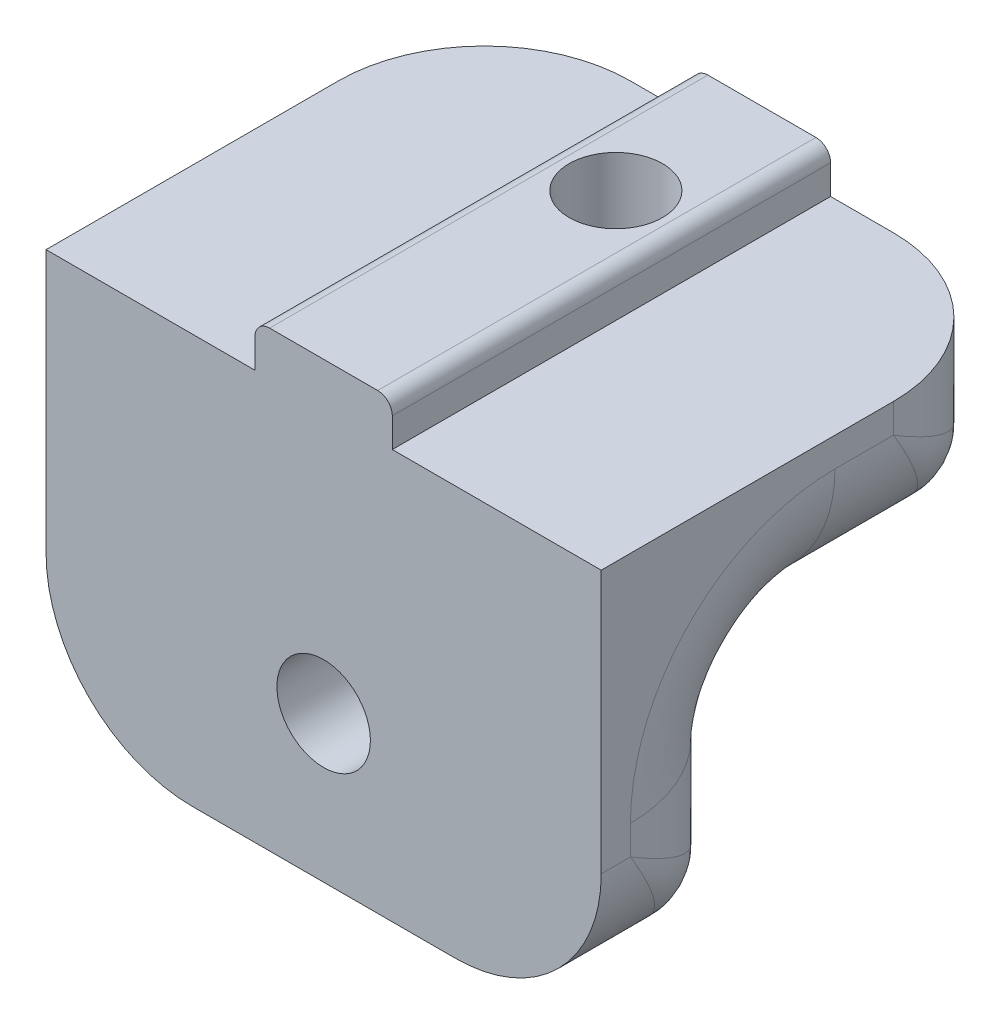
SolidWorks part; units mm, degrees
material "ABS"
ref_plane "Front" through (0, 0, 0) normal (0, 0, 1) x (1, 0, 0)
ref_plane "Top" through (0, 0, 0) normal (0, 1, 0) x (1, 0, 0)
ref_plane "Right" through (0, 0, 0) normal (1, 0, 0) x (0, 0, -1)
sketch "Esquisse1" plane through (0, 0, 0) normal (1, 0, 0) x (0, 0, -1)
  line L0 (15, 0) -> (0, 0)
  line L1 (0, 0) -> (0, -14)
  dimension "D1" = 90
  dimension "D2" = 15
  dimension "D3" = 14
extrude "Extru.-Mince1" add sketch "Esquisse1" along normal mid plane 19 thin thin type one direction reverse wall 6
fillet "Congé2" radius 2 3 edges at (0, -14, -6) (0, -6, -15) (0, -6, -6)
sketch "Esquisse2" plane through (0, 0, 0) normal (0, 1, 0) x (1, 0, 0)
  line L3 (9.5, 0) -> (-9.5, 0) construction
  line L4 (9.5, 15) -> (-9.5, 15) construction
  circle A1 centre (0, 10) radius 1.6
  dimension "D1" = 10
  dimension "D2" = 5
  dimension "D3" = 3.2
extrude "Enlèv. mat.-Extru.1" cut sketch "Esquisse2" against normal through all
sketch "Esquisse3" plane through (0, 0, 0) normal (0, 0, 1) x (1, 0, 0)
  line L0 (9.5, -14) -> (-9.5, -14) construction
  line L2 (9.5, 0) -> (-9.5, 0) construction
  circle A0 centre (0, -9) radius 1.6
  dimension "D1" = 5
  dimension "D2" = 3.2
  dimension "D3" = 9
extrude "Enlèv. mat.-Extru.2" cut sketch "Esquisse3" against normal through all
sketch "Esquisse4" plane through (0, 0, 0) normal (0, 1, 0) x (1, 0, 0)
  circle A0 centre (0, 10) radius 3
  circle A1 centre (0, 10) radius 1.6 construction
  dimension "D1" = 6
extrude "Enlèv. mat.-Extru.3" cut sketch "Esquisse4" against normal through all from offset 2.5 offset against normal yes
sketch "Esquisse5" plane through (0, 0, 0) normal (0, 0, 1) x (1, 0, 0)
  line L13 (-1.5877, -6.25) -> (-3.1754, -9)
  line L14 (-3.1754, -9) -> (-1.5877, -11.75)
  line L15 (-1.5877, -11.75) -> (1.5877, -11.75)
  line L16 (1.5877, -11.75) -> (3.1754, -9)
  line L17 (3.1754, -9) -> (1.5877, -6.25)
  line L18 (1.5877, -6.25) -> (-1.5877, -6.25)
  circle A3 centre (0, -9) radius 2.75 construction
  dimension "D1" = 5.5
extrude "Enlèv. mat.-Extru.4" cut sketch "Esquisse5" against normal blind 8 from offset 3 offset against normal yes
fillet "Congé1" radius 5 14 edges at (9.5, -2, -15) (-9.5, -2, -15) (9.5, -14, -2) (9.5, -13.4142, -5.4142) (9.5, -10, -6) (9.5, -6.5858, -6.5858) (9.5, -6, -10.5) (9.5, -5.4142, -14.4142) (-9.5, -14, -2) (-9.5, -13.4142, -5.4142) (-9.5, -10, -6) (-9.5, -6.5858, -6.5858) (-9.5, -6, -10.5) (-9.5, -5.4142, -14.4142)
sketch "Esquisse6" plane through (0, 0, 0) normal (0, 1, 0) x (1, 0, 0)
  line L0 (4.5, 15) -> (-4.5, 15) construction
  line L1 (-2.35, 15) -> (2.35, 15)
  line L2 (-2.35, 15) -> (-2.35, 0)
  line L3 (-2.35, 0) -> (2.35, 0)
  line L4 (2.35, 15) -> (2.35, 0)
  circle A0 centre (0, 10) radius 1.6 construction
  circle A1 centre (0, 10) radius 1.6
  dimension "D1" = 4.7
extrude "Boss.-Extru.1" add sketch "Esquisse6" along normal blind 1.5
fillet "Congé3" radius 0.5 2 edges at (-2.35, 1.5, -7.5) (2.35, 1.5, -7.5)
sketch "Esquisse7" plane through (0, 0, 0) normal (0, 0, 1) x (1, 0, 0)
  circle A1 centre (0, -9) radius 1.6 construction
  circle A2 centre (0, -9) radius 1.6
extrude "Boss.-Extru.2" [suppressed] add sketch "Esquisse7" against normal blind 0.2
